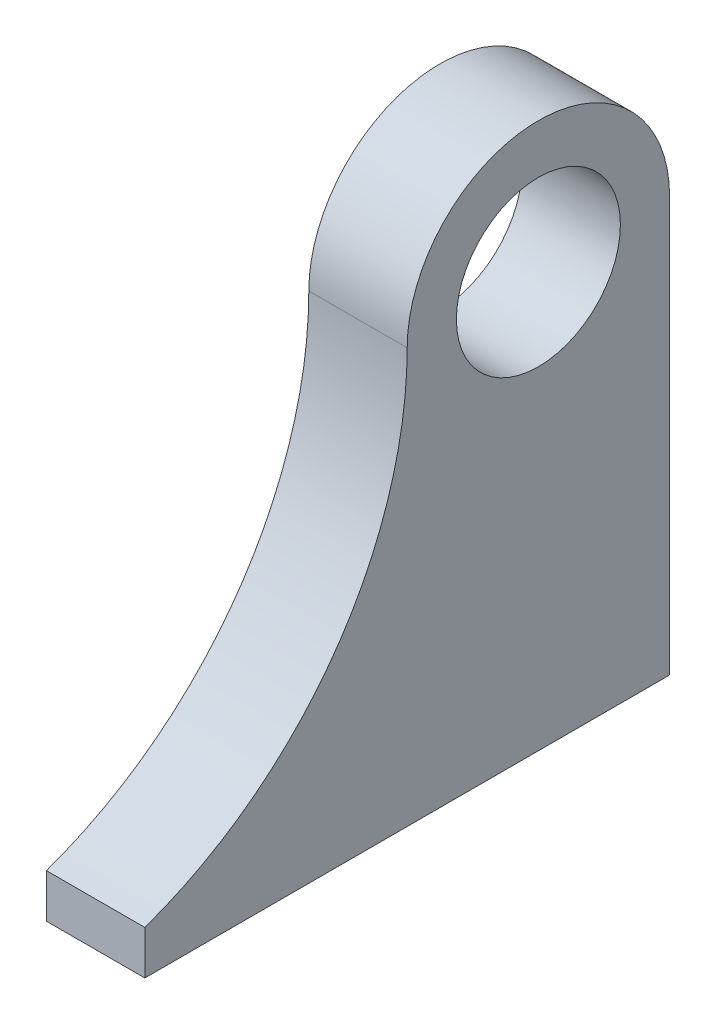
SolidWorks part; units mm, degrees
ref_plane "Alzado" through (0, 0, 0) normal (0, 0, 1) x (1, 0, 0)
ref_plane "Planta" through (0, 0, 0) normal (0, 1, 0) x (1, 0, 0)
ref_plane "Vista lateral" through (0, 0, 0) normal (1, 0, 0) x (0, 0, -1)
sketch "Croquis1" plane through (0, 0, 0) normal (0, 1, 0) x (1, 0, 0)
  line L0 (63.5, 63.5) -> (63.5, 390.652) construction
  line L1 (0, 0) -> (654.05, 0) construction
  line L2 (0, 0) -> (0, 454.152) construction
  line L3 (0, 454.152) -> (654.05, 454.152) construction
  line L4 (654.05, 0) -> (654.05, 454.152) construction
  line L5 (63.5, 390.652) -> (590.55, 390.652) construction
  line L6 (590.55, 63.5) -> (590.55, 390.652) construction
  line L7 (63.5, 63.5) -> (590.55, 63.5) construction
  line L8 (42.3333, 411.8187) -> (611.7167, 411.8187) construction
  line L9 (611.7167, 42.3333) -> (611.7167, 411.8187) construction
  line L10 (42.3333, 42.3333) -> (611.7167, 42.3333) construction
  line L11 (42.3333, 42.3333) -> (42.3333, 411.8187) construction
  line L12 (606.9542, 411.8187) -> (606.9542, 454.152) construction
  line L14 (606.9542, 454.152) -> (602.1917, 454.152)
  line L15 (606.9542, 454.152) -> (606.9542, 411.8187)
  line L16 (606.9542, 411.8187) -> (602.1917, 411.8187)
  line L17 (602.1917, 454.152) -> (602.1917, 411.8187)
  dimension "D1" = 654.05
  dimension "D2" = 454.152
  dimension "D3" = 42.3333
  dimension "D4" = 369.4853
  dimension "D5" = 63.5
  dimension "D6" = 569.3833
  dimension "D7" = 527.05
  dimension "D8" = 327.152
  dimension "D9" = 42.3333
  dimension "D10" = 4.7625
  dimension "D11" = 4.7625
  dimension "D12" = 42.3333
  dimension "D13" = 21.1667
extrude "Saliente-Extruir1" add sketch "Croquis1" along normal blind 26.416
sketch "Croquis2" plane through (606.9542, 0, 0) normal (1, 0, 0) x (0, 0, -1)
  line L0 (432.9853, 26.416) -> (432.9853, 0) construction
  line L1 (411.8187, 26.416) -> (454.152, 26.416) construction
  line L2 (411.8187, 0) -> (454.152, 0) construction
  line L3 (439.3353, 20.066) -> (439.3353, 0)
  line L4 (439.3353, 0) -> (413.9353, 0)
  line L5 (413.9353, 0) -> (411.8187, 0)
  line L6 (413.9353, 0) -> (411.8187, 0) construction
  line L7 (413.9353, 0) -> (413.9353, 2.12)
  line L8 (426.6353, 20.066) -> (432.9853, 20.066) construction
  line L9 (411.8187, 0) -> (411.8187, 26.416)
  line L10 (411.8187, 26.416) -> (454.152, 26.416)
  line L11 (454.152, 26.416) -> (454.152, 0)
  line L12 (454.152, 0) -> (439.3353, 0)
  circle A0 centre (432.9853, 20.066) radius 3.9688
  arc A1 (439.3353, 20.066) -> (426.6353, 20.066) centre (432.9853, 20.066) ccw
  arc A2 (413.9353, 2.12) -> (426.6353, 20.066) centre (407.6058, 20.066) ccw
  point P10 (432.9853, 20.066)
  line M4 (411.8187, 0) -> (454.152, 0)
  line M5 (454.152, 0) -> (454.152, 26.416)
  line M6 (454.152, 26.416) -> (411.8187, 26.416)
  line M7 (411.8187, 26.416) -> (411.8187, 0)
  dimension "D4" = 7.9375
  dimension "D5" = 2.12
  dimension "D3" = 6.35
  dimension "D1" = 25.4
  dimension "D2" = 2.1167
extrude "Cortar-Extruir1" cut sketch "Croquis2" against normal blind 25.4 contours L7 A2 A1 L10 M7 M4 | A1 L3 M4 M5 M6 | A0 region at (606.9542, 13.463, -446.5527) region at (606.9542, 15.9625, -418.5898) region at (606.9542, 20.066, -432.9853)
